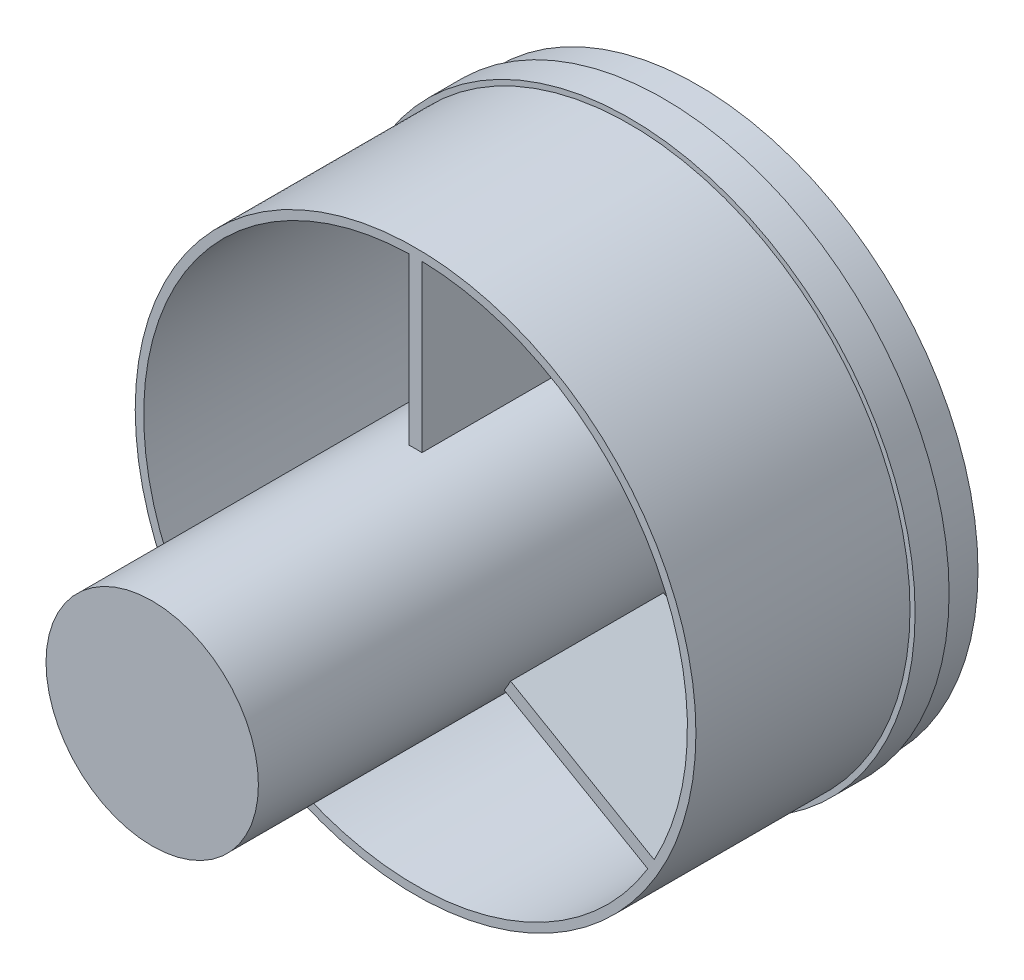
SolidWorks part; units mm, degrees
ref_plane "Plan de face" through (0, 0, 0) normal (0, 0, 1) x (1, 0, 0)
ref_plane "Plan de dessus" through (0, 0, 0) normal (0, 1, 0) x (1, 0, 0)
ref_plane "Plan de droite" through (0, 0, 0) normal (1, 0, 0) x (0, 0, -1)
sketch "Esquisse1" plane through (0, 0, 0) normal (0, 0, 1) x (1, 0, 0)
  circle A0 centre (0, 0) radius 33
  circle A1 centre (0, 0) radius 32
  dimension "D1" = 66
  dimension "D2" = 64
extrude "Boss.-Extru.1" add sketch "Esquisse1" along normal blind 4
sketch "Esquisse2" plane through (0, 0, 4) normal (0, 0, 1) x (1, 0, 0)
  circle A0 centre (0, 0) radius 32
  circle A1 centre (0, 0) radius 33.6
  circle A2 centre (0, 0) radius 32 construction
  dimension "D1" = 67.2
extrude "Boss.-Extru.2" add sketch "Esquisse2" along normal blind 4
sketch "Esquisse3" plane through (0, 0, 8) normal (0, 0, 1) x (1, 0, 0)
  circle A0 centre (0, 0) radius 32
  circle A1 centre (0, 0) radius 33
  circle A2 centre (0, 0) radius 32 construction
  dimension "D1" = 66
extrude "Boss.-Extru.3" add sketch "Esquisse3" along normal blind 25.2
sketch "Esquisse4" plane through (0, 0, 0) normal (0, 0, -1) x (-1, 0, 0)
  circle A0 centre (0, 0) radius 12.5
  dimension "D1" = 25
extrude "Boss.-Extru.4" add sketch "Esquisse4" along normal blind 12.5 and the other way offset from surface (64.2 mm away) 31 separate body other way up to face at (33, 0, 33.2)
fillet "Congé1" radius 12.5 1 edges at (-12.5, 0, -12.5)
sketch "Esquisse5" plane through (0, 0, 33.2) normal (0, 0, 1) x (1, 0, 0)
  line L0 (0, 0) -> (0, 33) construction
  line L1 (0.75, 32.9915) -> (0.75, 12.4775)
  line L2 (0.75, 12.4775) -> (-0.75, 12.4775)
  line L3 (-0.75, 12.4775) -> (-0.75, 32.9915)
  line L4 (-0.75, 32.9915) -> (0.75, 32.9915)
  line L5 (28.1965, -17.1453) -> (10.4308, -6.8883)
  line L6 (10.4308, -6.8883) -> (11.1808, -5.5892)
  line L7 (11.1808, -5.5892) -> (28.9465, -15.8462)
  line L8 (28.9465, -15.8462) -> (28.1965, -17.1453)
  line L9 (-28.9465, -15.8462) -> (-11.1808, -5.5892)
  line L10 (-11.1808, -5.5892) -> (-10.4308, -6.8883)
  line L11 (-10.4308, -6.8883) -> (-28.1965, -17.1453)
  line L12 (-28.1965, -17.1453) -> (-28.9465, -15.8462)
  circle A0 centre (0, 0) radius 33 construction
  circle A1 centre (0, 0) radius 12.5 construction
  circle A2 centre (0, 0) radius 33 construction
  point P28 (0, 0)
  dimension "D1" = 1.5
  dimension "D2" = 3
extrude "Boss.-Extru.5" add sketch "Esquisse5" against normal blind 18
